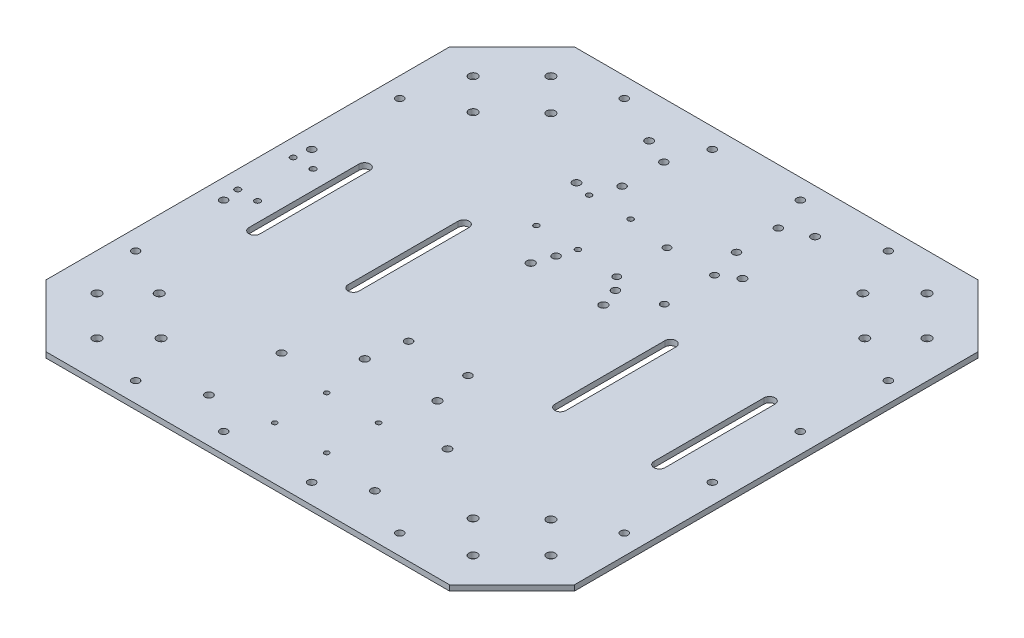
SolidWorks part; units mm, degrees
ref_plane "Front Plane" through (0, 0, 0) normal (0, 0, 1) x (1, 0, 0)
ref_plane "Top Plane" through (0, 0, 0) normal (0, 1, 0) x (1, 0, 0)
ref_plane "Right Plane" through (0, 0, 0) normal (1, 0, 0) x (0, 0, -1)
sketch "Sketch1" plane through (0, 0, 0) normal (0, 1, 0) x (1, 0, 0)
  line L0 (-61.766, 15.7353) -> (-25.845, 51.6564)
  line L1 (-61.766, 51.6564) -> (243.034, 51.6564)
  line L2 (-61.766, 51.6564) -> (-61.766, -253.1436)
  line L3 (-61.766, -253.1436) -> (243.034, -253.1436)
  line L4 (243.034, 51.6564) -> (243.034, -253.1436)
  line L5 (90.634, 95.069) -> (90.634, -294.9418) construction
  line L6 (-86.5248, -100.7436) -> (277.558, -100.7436) construction
  line L7 (243.034, 15.7353) -> (207.1129, 51.6564)
  line L8 (243.034, -217.2226) -> (207.1129, -253.1436)
  line L9 (-61.766, -217.2226) -> (-25.845, -253.1436)
  point P8 (90.634, 51.6564)
  point P11 (-61.766, -100.7436)
  dimension "D1" = 304.8
  dimension "D2" = 304.8
  dimension "D3" = 45
  dimension "D4" = 50.8
extrude "Boss-Extrude1" add sketch "Sketch1" along normal blind 3.175 contours L2 L9 L3 L8 L4 L7 L1 L0 region at (90.634, 0, 100.7436)
sketch "Sketch2" plane through (0, 3.175, 0) normal (0, 1, 0) x (1, 0, 0)
  line L0 (-40.323, 7.7627) -> (-22.3625, -10.1978) construction
  line L1 (-17.8724, 30.2133) -> (0.6409, 11.7001) construction
  line L2 (-43.8055, 33.6958) -> (20.8232, -30.9329) construction
  line L3 (-61.766, 15.7353) -> (-25.845, 51.6564) construction
  line L7 (90.634, 51.6564) -> (90.634, -253.1436) construction
  line L8 (-25.845, 51.6564) -> (207.1129, 51.6564) construction
  line L9 (-25.845, -253.1436) -> (207.1129, -253.1436) construction
  line L10 (-61.766, -100.7436) -> (243.034, -100.7436) construction
  line L11 (-61.766, 15.7353) -> (-61.766, -217.2226) construction
  line L12 (243.034, 15.7353) -> (243.034, -217.2226) construction
  circle A0 centre (-17.8724, 30.2133) radius 2.4638
  circle A1 centre (0.6409, 11.7001) radius 2.4638
  circle A2 centre (-22.3625, -10.1978) radius 2.4638
  circle A3 centre (-40.323, 7.7627) radius 2.4638
  circle A4 centre (203.6304, -10.1978) radius 2.4638
  circle A5 centre (221.5909, 7.7627) radius 2.4638
  circle A6 centre (180.627, 11.7001) radius 2.4638
  circle A7 centre (199.1403, 30.2133) radius 2.4638
  circle A8 centre (-22.3625, -191.2895) radius 2.4638
  circle A9 centre (-40.323, -209.25) radius 2.4638
  circle A10 centre (-17.8724, -231.7006) radius 2.4638
  circle A11 centre (0.6409, -213.1873) radius 2.4638
  circle A12 centre (221.5909, -209.25) radius 2.4638
  circle A13 centre (199.1403, -231.7006) radius 2.4638
  circle A14 centre (180.627, -213.1873) radius 2.4638
  circle A15 centre (203.6304, -191.2895) radius 2.4638
  dimension "D3" = 4.9276
  dimension "D4" = 4.9276
  dimension "D5" = 4.9276
  dimension "D6" = 4.9276
  dimension "D1" = 25.4
  dimension "D2" = 31.75
  dimension "D7" = 15.875
extrude "Cut-Extrude1" cut sketch "Sketch2" against normal blind 6.35
sketch "Sketch3" plane through (0, 3.175, 0) normal (0, 1, 0) x (1, 0, 0)
  line L0 (-61.766, -100.7436) -> (278.5513, -100.7436) construction
  line L2 (-61.766, 15.7353) -> (-61.766, -217.2226) construction
  line L3 (90.634, 51.6564) -> (90.634, -273.1997) construction
  line L4 (-25.845, 51.6564) -> (207.1129, 51.6564) construction
  circle A0 centre (73.489, -58.1986) radius 2.159
  circle A1 centre (107.779, -58.1986) radius 2.159
  circle A2 centre (73.489, -143.2886) radius 2.159
  circle A3 centre (107.779, -143.2886) radius 2.159
  point P10 (-61.766, -100.7436)
  dimension "D3" = 4.318
  dimension "D4" = 4.318
  dimension "D5" = 4.318
  dimension "D6" = 4.318
  dimension "D1" = 34.29
  dimension "D2" = 85.09
  dimension "D7" = 42.545
  dimension "D8" = 17.145
extrude "Cut-Extrude2" cut sketch "Sketch3" against normal blind 6.35
sketch "Sketch4" plane through (0, 3.175, 0) normal (0, 1, 0) x (1, 0, 0)
  line L0 (90.634, 51.6564) -> (90.634, -36.4614) construction
  line L1 (-25.845, 51.6564) -> (207.1129, 51.6564) construction
  line L2 (-61.766, -100.7436) -> (257.447, -100.7436) construction
  line L3 (-61.766, 15.7353) -> (-61.766, -217.2226) construction
  circle A0 centre (42.755, 26.2564) radius 2.2225
  circle A1 centre (138.513, 26.2564) radius 2.2225
  circle A2 centre (42.755, -15.6536) radius 2.2225
  circle A3 centre (138.513, -15.6536) radius 2.2225
  circle A4 centre (138.513, -185.8336) radius 2.2225
  circle A5 centre (42.755, -185.8336) radius 2.2225
  circle A6 centre (138.513, -227.7436) radius 2.2225
  circle A7 centre (42.755, -227.7436) radius 2.2225
  circle A8 centre (69.679, -68.9936) radius 2.286
  circle A9 centre (111.589, -68.9936) radius 2.286
  circle A10 centre (69.679, -164.7516) radius 2.286
  circle A11 centre (111.589, -164.7516) radius 2.286
  dimension "D1" = 4.445
  dimension "D2" = 4.445
  dimension "D3" = 4.445
  dimension "D4" = 4.445
  dimension "D9" = 4.572
  dimension "D10" = 4.572
  dimension "D13" = 4.572
  dimension "D14" = 4.572
  dimension "D5" = 95.758
  dimension "D6" = 41.91
  dimension "D7" = 47.879
  dimension "D8" = 25.4
  dimension "D11" = 41.91
  dimension "D12" = 20.955
  dimension "D15" = 95.758
  dimension "D16" = 31.75
extrude "Cut-Extrude3" cut sketch "Sketch4" against normal through all
sketch "Sketch5" plane through (0, 3.175, 0) normal (0, 1, 0) x (1, 0, 0)
  line L0 (-61.766, -100.7436) -> (105.2484, -100.7436) construction
  line L1 (-61.766, 15.7353) -> (-61.766, -217.2226) construction
  circle A0 centre (-51.606, -84.7416) radius 1.651
  circle A1 centre (-40.176, -84.7416) radius 1.651
  circle A2 centre (-40.176, -116.7456) radius 1.651
  circle A3 centre (-51.606, -116.7456) radius 1.651
  dimension "D1" = 3.302
  dimension "D2" = 3.302
  dimension "D3" = 11.43
  dimension "D4" = 16.002
  dimension "D5" = 10.16
extrude "Cut-Extrude4" cut sketch "Sketch5" against normal through all
sketch "Sketch6" plane through (0, 3.175, 0) normal (0, 1, 0) x (1, 0, 0)
  line L0 (243.034, 15.7353) -> (243.034, -217.2226) construction
  line L1 (-25.845, 51.6564) -> (207.1129, 51.6564) construction
  line L2 (90.634, 51.6564) -> (90.634, -253.1436) construction
  line L3 (-25.845, -253.1436) -> (207.1129, -253.1436) construction
  line L4 (-61.766, 15.7353) -> (-61.766, -217.2226) construction
  circle A0 centre (101.302, -22.0036) radius 2.032
  circle A1 centre (101.302, -50.9596) radius 2.032
  circle A2 centre (128.734, -50.9596) radius 2.032
  circle A3 centre (128.734, -22.0036) radius 2.032
  circle A4 centre (57.614, 19.9064) radius 2.159
  circle A5 centre (57.614, -4.2236) radius 2.159
  circle A6 centre (123.654, -4.2236) radius 2.159
  circle A7 centre (123.654, 19.9064) radius 2.159
  circle A8 centre (75.648, -192.6916) radius 1.397
  circle A9 centre (75.648, -222.6636) radius 1.397
  circle A10 centre (105.62, -222.6636) radius 1.397
  circle A11 centre (105.62, -192.6916) radius 1.397
  circle A12 centre (52.534, -18.1936) radius 1.55
  circle A13 centre (52.534, -48.5936) radius 1.55
  circle A14 centre (76.534, -18.1936) radius 1.55
  circle A15 centre (76.534, -48.5936) radius 1.55
  dimension "D1" = 4.064
  dimension "D6" = 4.318
  dimension "D7" = 4.318
  dimension "D10" = 2.794
  dimension "D11" = 2.794
  dimension "D15" = 3.1
  dimension "D16" = 3.1
  dimension "D18" = 3.1
  dimension "D19" = 3.1
  dimension "D2" = 27.432
  dimension "D3" = 28.956
  dimension "D4" = 114.3
  dimension "D5" = 73.66
  dimension "D8" = 33.02
  dimension "D9" = 24.13
  dimension "D12" = 14.986
  dimension "D13" = 29.972
  dimension "D14" = 30.48
  dimension "D17" = 30.4
  dimension "D20" = 24
  dimension "D21" = 31.75
  dimension "D22" = 114.3
  dimension "D23" = 69.85
extrude "Cut-Extrude5" cut sketch "Sketch6" against normal through all
sketch "Sketch7" plane through (0, 3.175, 0) normal (0, 1, 0) x (1, 0, 0)
  line L0 (90.634, 51.6564) -> (90.634, -272.7763) construction
  line L1 (-25.845, 51.6564) -> (207.1129, 51.6564) construction
  line L2 (-61.766, -100.7436) -> (338.9555, -100.7436) construction
  line L3 (-61.766, 15.7353) -> (-61.766, -217.2226) construction
  circle A0 centre (65.234, 40.2264) radius 2.159
  circle A1 centre (14.434, 40.2264) radius 2.159
  circle A2 centre (-50.336, -75.3436) radius 2.159
  circle A3 centre (-50.336, -24.5436) radius 2.159
  circle A4 centre (231.604, -24.5436) radius 2.159
  circle A5 centre (231.604, -75.3436) radius 2.159
  circle A6 centre (166.834, 40.2264) radius 2.159
  circle A7 centre (116.034, 40.2264) radius 2.159
  circle A8 centre (116.034, -241.7136) radius 2.159
  circle A9 centre (166.834, -241.7136) radius 2.159
  circle A10 centre (231.604, -126.1436) radius 2.159
  circle A11 centre (231.604, -176.9436) radius 2.159
  circle A12 centre (-50.336, -176.9436) radius 2.159
  circle A13 centre (-50.336, -126.1436) radius 2.159
  circle A14 centre (14.434, -241.7136) radius 2.159
  circle A15 centre (65.234, -241.7136) radius 2.159
  dimension "D1" = 4.318
  dimension "D2" = 4.318
  dimension "D6" = 4.318
  dimension "D7" = 4.318
  dimension "D3" = 25.4
  dimension "D4" = 50.8
  dimension "D5" = 11.43
  dimension "D8" = 25.4
  dimension "D9" = 50.8
  dimension "D10" = 11.43
extrude "Cut-Extrude6" cut sketch "Sketch7" against normal through all
sketch "Sketch8" plane through (0, 3.175, 0) normal (0, 1, 0) x (1, 0, 0)
  line L0 (-26.206, -68.9936) -> (-26.206, -132.4936) construction
  line L1 (-23.031, -68.9936) -> (-23.031, -132.4936)
  line L2 (-29.381, -68.9936) -> (-29.381, -132.4936)
  line L3 (30.944, -68.9936) -> (30.944, -132.4936) construction
  line L4 (34.119, -68.9936) -> (34.119, -132.4936)
  line L5 (27.769, -68.9936) -> (27.769, -132.4936)
  line L7 (243.034, 15.7353) -> (243.034, -217.2226) construction
  line L8 (90.634, 51.6564) -> (90.634, -227.3263) construction
  line L9 (-25.845, 51.6564) -> (207.1129, 51.6564) construction
  line L10 (207.474, -68.9936) -> (207.474, -132.4936) construction
  line L11 (204.299, -68.9936) -> (204.299, -132.4936)
  line L12 (210.649, -68.9936) -> (210.649, -132.4936)
  line L13 (150.324, -68.9936) -> (150.324, -132.4936) construction
  line L14 (147.149, -68.9936) -> (147.149, -132.4936)
  line L15 (153.499, -68.9936) -> (153.499, -132.4936)
  arc A0 (-23.031, -68.9936) -> (-29.381, -68.9936) centre (-26.206, -68.9936) ccw
  arc A1 (-29.381, -132.4936) -> (-23.031, -132.4936) centre (-26.206, -132.4936) ccw
  arc A2 (34.119, -68.9936) -> (27.769, -68.9936) centre (30.944, -68.9936) ccw
  arc A3 (27.769, -132.4936) -> (34.119, -132.4936) centre (30.944, -132.4936) ccw
  arc A4 (204.299, -68.9936) -> (210.649, -68.9936) centre (207.474, -68.9936) cw
  arc A5 (210.649, -132.4936) -> (204.299, -132.4936) centre (207.474, -132.4936) cw
  arc A6 (147.149, -68.9936) -> (153.499, -68.9936) centre (150.324, -68.9936) cw
  arc A7 (153.499, -132.4936) -> (147.149, -132.4936) centre (150.324, -132.4936) cw
  point P2 (-26.206, -100.7436)
  point P7 (30.944, -100.7436)
  point P14 (90.634, -87.835)
  point P17 (243.034, -100.7436)
  point P24 (207.474, -100.7436)
  point P31 (150.324, -100.7436)
  dimension "D5" = 6.35
  dimension "D1" = 63.5
  dimension "D2" = 63.5
  dimension "D3" = 50.8
  dimension "D4" = 59.69
  dimension "D6" = 6.35
extrude "Cut-Extrude8" cut sketch "Sketch8" against normal through all
